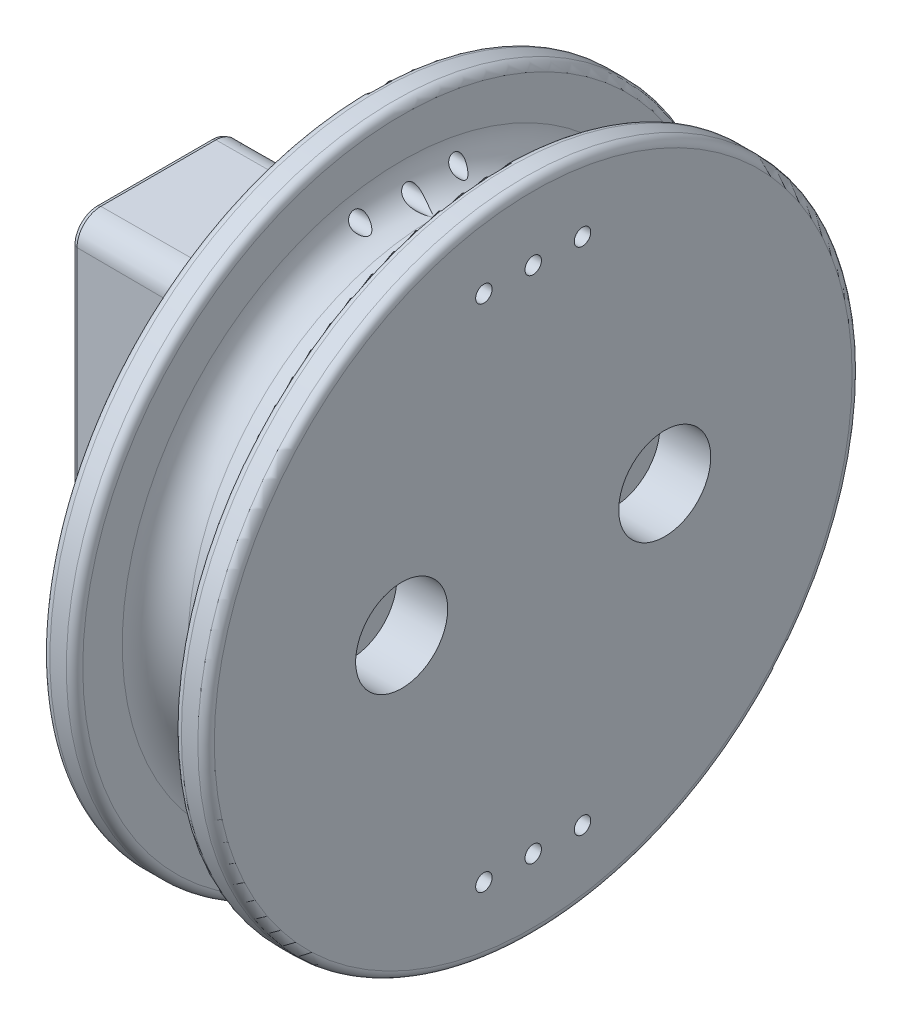
SolidWorks part; units mm, degrees
ref_plane "Ebene vorne" through (0, 0, 0) normal (0, 0, 1) x (1, 0, 0)
ref_plane "Ebene oben" through (0, 0, 0) normal (0, 1, 0) x (1, 0, 0)
ref_plane "Ebene rechts" through (0, 0, 0) normal (1, 0, 0) x (0, 0, -1)
ref_plane "Ebene1" through (3, 0, 0) normal (1, 0, 0) x (0, 0, -1)
sketch "Skizze1" plane through (0, 0, 0) normal (1, 0, 0) x (0, 0, -1)
  circle A0 centre (0, 0) radius 11.5
  dimension "D1" = 23
extrude "Aufsatz-Linear austragen1" add sketch "Skizze1" along normal blind 13
sketch "Skizze2" plane through (0, 0, 0) normal (1, 0, 0) x (0, 0, -1)
  line L0 (0, 17.4813) -> (0, -19.2829) construction
  line L1 (19.1866, 0) -> (-17.8656, 0) construction
  line L2 (5, -7.5) -> (5, 7.5)
  line L3 (3.5, 9) -> (-3.5, 9)
  line L4 (-5, -7.5) -> (-5, 7.5)
  line L5 (3.5, -9) -> (-3.5, -9)
  arc A0 (-5, -7.5) -> (-3.5, -9) centre (-3.5, -7.5) ccw
  arc A1 (3.5, -9) -> (5, -7.5) centre (3.5, -7.5) ccw
  arc A2 (-5, 7.5) -> (-3.5, 9) centre (-3.5, 7.5) cw
  arc A3 (5, 7.5) -> (3.5, 9) centre (3.5, 7.5) ccw
  point P9 (0, 9)
  point P10 (0, -9)
  point P12 (-5, 0)
  point P13 (5, 0)
  point P15 (-5, -9)
  point P18 (5, -9)
  point P21 (-5, 9)
  point P24 (5, 9)
  dimension "D3" = 1.5
  dimension "D1" = 18
  dimension "D2" = 10
extrude "Aufsatz-Linear austragen2" add sketch "Skizze2" against normal blind 10 draft 0.3
sketch "Skizze3" plane through (0, 0, 0) normal (1, 0, 0) x (0, 0, -1)
  line L0 (0, 16.115) -> (0, -14.9006) construction
  line L1 (15.3013, 0) -> (-17.9263, 0) construction
  line L2 (3, -6.5) -> (3, 6.5)
  line L3 (2, 7.5) -> (-2, 7.5)
  line L4 (-3, -6.5) -> (-3, 6.5)
  line L5 (2, -7.5) -> (-2, -7.5)
  arc A0 (3, -6.5) -> (2, -7.5) centre (2, -6.5) cw
  arc A1 (-2, -7.5) -> (-3, -6.5) centre (-2, -6.5) cw
  arc A2 (-3, 6.5) -> (-2, 7.5) centre (-2, 6.5) cw
  arc A3 (3, 6.5) -> (2, 7.5) centre (2, 6.5) ccw
  point P9 (0, 7.5)
  point P10 (0, -7.5)
  point P12 (-3, 0)
  point P13 (3, 0)
  point P15 (3, -7.5)
  point P18 (-3, -7.5)
  point P21 (-3, 7.5)
  point P24 (3, 7.5)
  dimension "D3" = 1
  dimension "D1" = 6
  dimension "D2" = 15
extrude "Schnitt-Linear austragen1" [suppressed] cut sketch "Skizze3" against normal through all and the other way through all
ref_axis "Achse1" through (11, 0, 0) along (-1, 0, 0)
hole_wizard "Stirnsenkung für M3 Zylinderschraube mit Innensechskant1" positions "Skizze5" profile "Skizze4" counterbore size "M3" standard "ANSI Metrisch" end condition through all
sketch "Skizze5" plane through (13, 0, 0) normal (1, 0, 0) x (0, 0, -1)
  line L0 (-20.2738, 0) -> (19.2387, 0) construction
  line L3 (0, 16.0743) -> (0, -16.0332) construction
  point P0 (8, 0)
  point P16 (-8, 0)
  dimension "D1" = 16
sketch "Skizze4" plane through (13, 0, -8) normal (0, 1, 0) x (0, 0, -1)
  line L0 (0, 0) -> (0, 23)
  line L1 (0, 23) -> (1.55, 23)
  line L3 (1.55, 23) -> (1.55, 3.1)
  line L4 (1.55, 3.1) -> (2.8, 3.1)
  line L5 (2.8, 3.1) -> (2.8, 0)
  line L7 (2.8, 0) -> (0, 0)
  line L11 (0, -6.35) -> (0, 107.95) construction
  dimension "Bohrerdurchmesser" = 3.1
  dimension "Bohrungstiefe" = 23
  dimension "Senkdurchmesser2" = 5.6
  dimension "Senktiefe2" = 3.1
sketch "Skizze7" plane through (13, 0, 0) normal (1, 0, 0) x (0, 0, -1)
  line L0 (0, 19.4022) -> (0, -18.8869) construction
  line L1 (-17.5053, 0) -> (18.7115, 0) construction
  line L2 (0, 0) -> (-14.4012, -10.0838) construction
  circle A0 centre (-7.3724, -5.1622) radius 1.25
  circle A1 centre (7.3724, -5.1622) radius 1.25
  circle A2 centre (7.3724, 5.1622) radius 1.25
  circle A3 centre (-7.3724, 5.1622) radius 1.25
  circle A4 centre (0, 0) radius 9 construction
  dimension "D1" = 2.5
  dimension "D3" = 35
  dimension "D2" = 18
extrude "Schnitt-Linear austragen2" [suppressed] cut sketch "Skizze7" against normal through all
sketch "Skizze6" plane through (3, 0, 0) normal (1, 0, 0) x (0, 0, -1)
  circle A0 centre (0, 0) radius 11.5
  circle A1 centre (0, 0) radius 19.9
  circle A2 centre (0, 0) radius 11.5 construction
  dimension "D1" = 39.8
extrude "Aufsatz-Linear austragen3" add sketch "Skizze6" along normal blind 10
fillet "Verrundung1" radius 1 8 edges at (0, -8.5607, 4.5607) (0, 0, 5) (0, 8.5607, 4.5607) (0, 9, 0) (0, 8.5607, -4.5607) (0, 0, -5) (0, -8.5607, -4.5607) (0, -9, 0)
chamfer "Fase1" [suppressed] distance 0.2 angle 45
chamfer "Fase2" distance 0.2 angle 20 8 edges at (-10, 0, 4.9476) (-10, -8.5236, 4.5236) (-10, 8.5236, 4.5236) (-10, -8.9476, 0) (-10, 8.9476, 0) (-10, -8.5236, -4.5236) (-10, 8.5236, -4.5236) (-10, 0, -4.9476) first distance on face at (-5.4974, 0, 4.9712) first distance on face at (-5.4974, -8.388, 4.388) first distance on face at (-5.4974, 8.388, 4.388) first distance on face at (-5.4974, -8.9712, 0) first distance on face at (-5.4974, 8.9712, 0) first distance on face at (-5.4974, -8.388, -4.388) first distance on face at (-5.4974, 8.388, -4.388) first distance on face at (-5.4974, 0, -4.9712)
sketch "Skizze8" plane through (0, 0, 0) normal (0, 1, 0) x (1, 0, 0)
  line L0 (8, -57.8615) -> (8, -40.4956) construction
  line L1 (3, 19.9) -> (3, -19.9) construction
  line L2 (13, -19.9) -> (13, 19.9) construction
  line L3 (11, -19.9) -> (11, -15)
  line L4 (3, -19.9) -> (13, -19.9) construction
  line L5 (11, -15) -> (5, -15)
  line L6 (5, -15) -> (5, -19.9)
  line L7 (5, -19.9) -> (11, -19.9)
  dimension "D1" = 6
  dimension "D2" = 15
revolve "Schnitt-Rotation1" cut sketch "Skizze8" angle 360 about axis through (11, 0, 0) along (-1, 0, 0)
fillet "Verrundung2" radius 2 2 edges at (11, 0, -15) (5, 0, -15)
fillet "Verrundung3" radius 0.5 4 edges at (13, 0, -19.9) (11, 0, -19.9) (5, 0, -19.9) (3, 0, -19.9)
fillet "Verrundung4" radius 2 1 edges at (3, 0, -11.5)
sketch "Skizze9" plane through (0, 0, 0) normal (1, 0, 0) x (0, 0, -1)
  line L0 (0, 0) -> (-20.5061, 20.5061) construction
  line L1 (0, 55.2166) -> (0, -54.4117) construction
  line L2 (-70.2668, 0) -> (56.8174, 0) construction
  circle A0 centre (-20.5061, 20.5061) radius 13.5
  circle A1 centre (-20.5061, -20.5061) radius 13.5
  circle A2 centre (20.5061, -20.5061) radius 13.5
  circle A3 centre (20.5061, 20.5061) radius 13.5
  dimension "D1" = 27
  dimension "D2" = 29
  dimension "D3" = 45
extrude "Schnitt-Linear austragen3" [suppressed] cut sketch "Skizze9" along normal through all
fillet "Verrundung5" [suppressed] radius 3
ref_plane "Ebene2" through (8, 0, 0) normal (1, 0, 0) x (0, 0, -1)
sketch "Skizze10" plane through (8, 0, 0) normal (1, 0, 0) x (0, 0, -1)
  line L0 (0, -35.627) -> (0, 32.7044) construction
  line L1 (32.735, 0) -> (-28.6232, 0) construction
  line L2 (9.4173, -15.5) -> (-7.2607, -15.5) construction
  circle A0 centre (3, -15.5) radius 0.5
  circle A1 centre (-3, -15.5) radius 0.5
  circle A2 centre (0, -15.5) radius 0.5
  dimension "D1" = 1
  dimension "D2" = 6
  dimension "D3" = 15.5
extrude "Schnitt-Linear austragen4" cut sketch "Skizze10" along normal through all and the other way blind 10
mirror "Spiegeln1" about plane through (0, 0, 0) normal (0, 1, 0) of "Schnitt-Linear austragen4"
